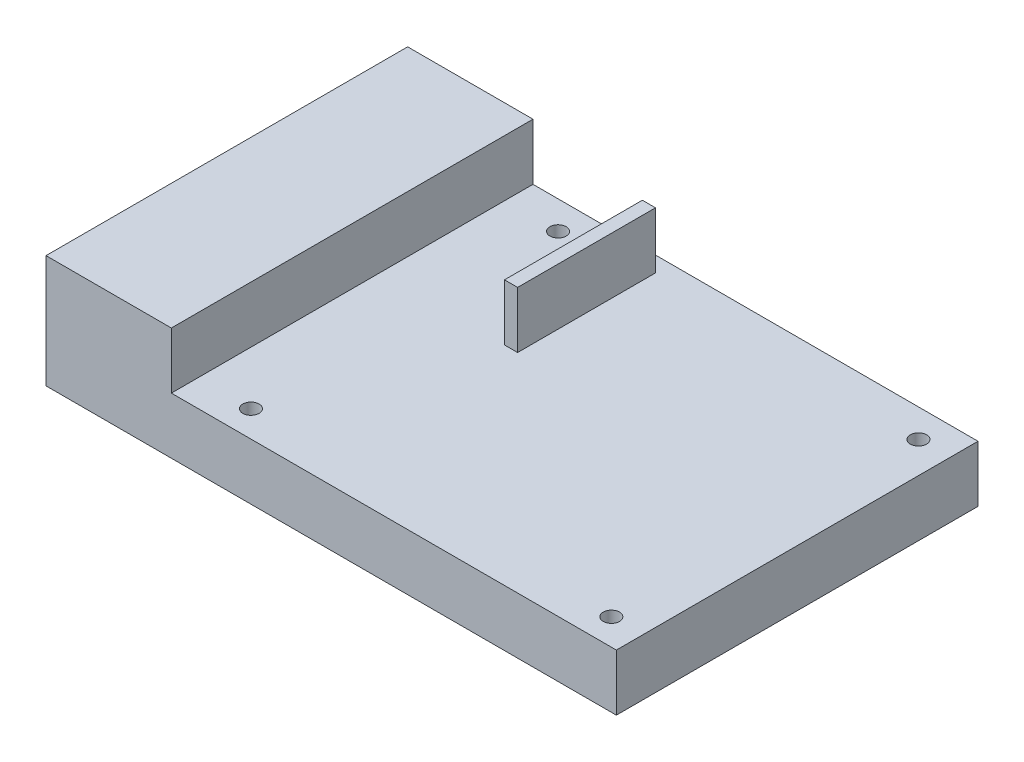
SolidWorks part; units mm, degrees
ref_plane "Front Plane" through (0, 0, 0) normal (0, 0, 1) x (1, 0, 0)
ref_plane "Top Plane" through (0, 0, 0) normal (0, 1, 0) x (1, 0, 0)
ref_plane "Right Plane" through (0, 0, 0) normal (1, 0, 0) x (0, 0, -1)
sketch "Sketch1" plane through (0, 0, 0) normal (0, 1, 0) x (1, 0, 0)
  line L0 (0, 0) -> (0, -57.7)
  line L1 (0, -57.7) -> (91, -57.7)
  line L2 (91, -57.7) -> (91, 0)
  line L3 (91, 0) -> (0, 0)
  line L4 (20, 0) -> (20, -57.7)
  line L5 (39.92, -2.4695) -> (39.92, -24.4695)
  line L6 (39.92, -24.4695) -> (42.0134, -24.4695)
  line L7 (42.0134, -24.4695) -> (42.0134, -2.4695)
  line L8 (42.0134, -2.4695) -> (39.92, -2.4695)
  circle A0 centre (28.5, -4.5) radius 1.3
  circle A1 centre (28.5, -53.5) radius 1.3
  circle A2 centre (86, -53.5) radius 1.3
  circle A3 centre (86, -4.5) radius 1.3
  point P29 (0, -28.85)
  dimension "D1" = 2.6
  dimension "D2" = 57.5
  dimension "D3" = 49
  dimension "D4" = 22
  dimension "D5" = 91
  dimension "D6" = 57.7
  dimension "D7" = 46.08
  dimension "D8" = 5
  dimension "D9" = 20
  dimension "D10" = 4.5
extrude "Boss-Extrude1" add sketch "Sketch1" along normal blind 18 contours L4 L3 L0 L1 | L8 L5 L6 L7 region at (10, 0, 28.85)
extrude "Boss-Extrude2" add sketch "Sketch1<3>" along normal blind 9 contours L3 L4 L1 L2 A3 A2 A1 A0 L8 L7 L6 L5 region at (55.6569, 0, 29.025)
sketch "Sketch1<3>" plane through (0, 0, 0) normal (0, 1, 0) x (1, 0, 0) same geometry as "Sketch1"
